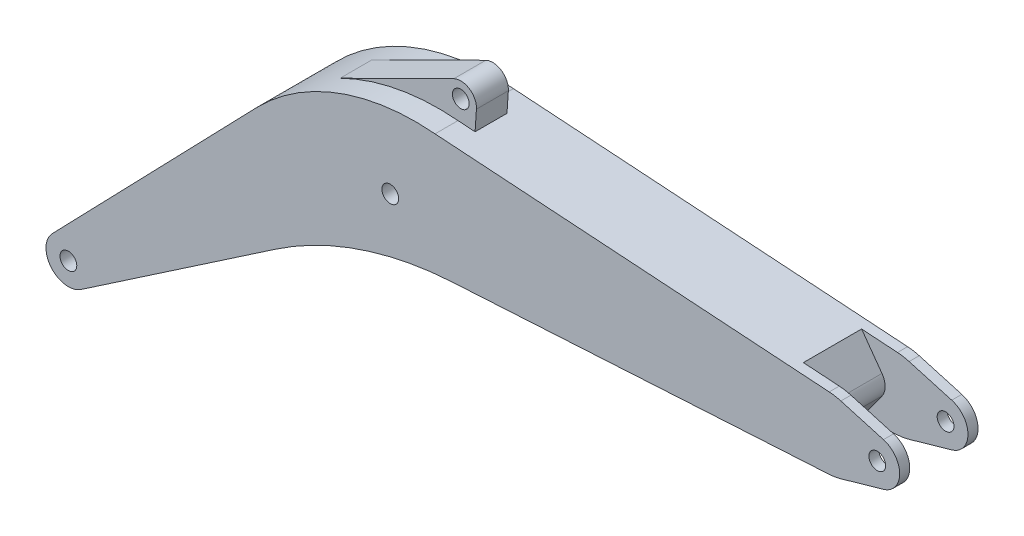
SolidWorks part; units mm, degrees
ref_plane "前视基准面" through (0, 0, 0) normal (0, 0, 1) x (1, 0, 0)
ref_plane "上视基准面" through (0, 0, 0) normal (0, 1, 0) x (1, 0, 0)
ref_plane "右视基准面" through (0, 0, 0) normal (1, 0, 0) x (0, 0, -1)
sketch "草图1" plane through (0, 0, 0) normal (0, 0, 1) x (1, 0, 0)
  line L0 (84.9387, 100.9448) -> (169.1185, 46.9656) construction
  line L1 (163.6, 91.5) -> (232.0719, 95.4882)
  line L2 (232.0719, 95.4882) -> (240.6992, 97.954)
  line L3 (160.6, 112.9) -> (232.0719, 108.1118)
  line L4 (232.0719, 108.1118) -> (240.6992, 105.646)
  line L5 (128.7, 101) -> (92.2246, 63.2806)
  line L6 (97.3478, 57.1913) -> (132.1, 80.8)
  line L7 (95.1, 60.5) -> (239.6, 60.5) construction
  line L8 (239.6, 60.5) -> (239.6, 101.8) construction
  line L9 (239.6, 101.8) -> (95.1, 101.8) construction
  line L10 (95.1, 101.8) -> (95.1, 60.5) construction
  line L11 (152.6, 99.6031) -> (152.6, 60.5) construction
  line L12 (132.1, 80.8) -> (132.1, 60.5) construction
  line L13 (128.7, 101) -> (128.7, 60.5) construction
  line L14 (160.6, 112.9) -> (160.6, 60.5) construction
  line L16 (163.6, 91.5) -> (163.6, 60.5)
  arc A0 (128.7, 101) -> (160.6, 112.9) centre (157.1228, 73.5146) cw
  arc A1 (92.2246, 63.2806) -> (97.3478, 57.1913) centre (95.1, 60.5) ccw
  arc A2 (132.1, 80.8) -> (163.6, 91.5) centre (167.2357, 29.0799) cw
  arc A3 (240.6992, 105.646) -> (240.6992, 97.954) centre (239.6, 101.8) cw
  circle A4 centre (239.6, 101.8) radius 1.5
  circle A5 centre (152.6, 99.6031) radius 1.5
  circle A6 centre (95.1, 60.5) radius 1.5
  dimension "D2" = 4
  dimension "D3" = 3
  dimension "D4" = 4
  dimension "D1" = 100
  dimension "D6" = 33.6
  dimension "D7" = 31
  dimension "D8" = 40.5
  dimension "D10" = 95.1
  dimension "D11" = 60.5
  dimension "D12" = 144.5
  dimension "D13" = 41.3
  dimension "D14" = 3.4
  dimension "D15" = 20.3
  dimension "D16" = 20.5
  dimension "D17" = 8
  dimension "D18" = 3
  dimension "D19" = 52.4
extrude "凸台-拉伸1" add sketch "草图1" along normal blind 7 and the other way blind 7 contours A3 L4 L3 A0 L5 A1 L6 A2 L1 L2 A6 A5 A4 region at (163.6972, 95.3089, 0)
fillet "圆角1" radius 10 2 edges at (232.0719, 95.4882, 0) (232.0719, 108.1118, 0)
sketch "草图3" plane through (0, 0, 0) normal (0, 0, 1) x (1, 0, 0)
  line L0 (160.6, 112.9) -> (231.0129, 108.1827) construction
  line L1 (163.6514, 112.6956) -> (163.8937, 116.3128)
  line L3 (160.6, 112.9) -> (232.0719, 108.1118) construction
  line L4 (159.8555, 119.0082) -> (139.5495, 108.9333)
  line L10 (163.6, 91.5) -> (230.9683, 95.4239)
  line L11 (233.1349, 95.792) -> (240.6992, 97.954)
  line L12 (240.6992, 105.646) -> (233.0925, 107.8201)
  line L13 (231.0129, 108.1827) -> (160.6, 112.9)
  line L14 (128.7, 101) -> (92.2246, 63.2806)
  line L15 (97.3478, 57.1913) -> (132.1, 80.8)
  line L16 (163.6, 91.5) -> (230.9683, 95.4239)
  line L17 (233.1349, 95.792) -> (240.6992, 97.954)
  line L18 (240.6992, 105.646) -> (233.0925, 107.8201)
  line L19 (231.0129, 108.1827) -> (160.6, 112.9)
  line L20 (128.7, 101) -> (92.2246, 63.2806)
  line L21 (97.3478, 57.1913) -> (132.1, 80.8)
  arc A0 (160.6, 112.9) -> (128.7, 101) centre (157.1228, 73.5146) ccw construction
  arc A1 (159.8555, 119.0082) -> (163.8937, 116.3128) centre (161.1, 116.5) cw
  circle A2 centre (161.1, 116.5) radius 1.5
  arc A9 (230.9683, 95.4239) -> (233.1349, 95.792) centre (230.3868, 105.407) ccw
  arc A10 (240.6992, 97.954) -> (240.6992, 105.646) centre (239.6, 101.8) ccw
  arc A11 (233.0925, 107.8201) -> (231.0129, 108.1827) centre (230.3444, 98.2051) ccw
  arc A12 (160.6, 112.9) -> (128.7, 101) centre (157.1228, 73.5146) ccw
  arc A13 (92.2246, 63.2806) -> (97.3478, 57.1913) centre (95.1, 60.5) ccw
  arc A14 (163.6, 91.5) -> (132.1, 80.8) centre (167.2357, 29.0799) ccw
  arc A15 (230.9683, 95.4239) -> (233.1349, 95.792) centre (230.3868, 105.407) ccw
  arc A16 (240.6992, 97.954) -> (240.6992, 105.646) centre (239.6, 101.8) ccw
  arc A17 (233.0925, 107.8201) -> (231.0129, 108.1827) centre (230.3444, 98.2051) ccw
  arc A18 (160.6, 112.9) -> (128.7, 101) centre (157.1228, 73.5146) ccw
  arc A19 (92.2246, 63.2806) -> (97.3478, 57.1913) centre (95.1, 60.5) ccw
  arc A20 (163.6, 91.5) -> (132.1, 80.8) centre (167.2357, 29.0799) ccw
  dimension "D1" = 3
  dimension "D5" = 2.8
  dimension "D3" = 56
  dimension "D4" = 66
  dimension "D2" = 0
extrude "凸台-拉伸2" add sketch "草图3" along normal blind 2.9 and the other way blind 2.8 contours L1 A1 L4 A2 region at (156.7685, 114.8999, 0)
sketch "草图4" plane through (0, 0, 0) normal (0, 0, 1) x (1, 0, 0)
  line L0 (224.6, 108.6124) -> (228.2365, 103.5503)
  line L1 (160.6, 112.9) -> (232.0719, 108.1118) construction
  line L2 (228.2256, 100.0347) -> (224.6, 95.053)
  line L3 (163.6, 91.5) -> (232.0719, 95.4882) construction
  line L4 (239.6, 101.8) -> (224.6, 101.8) construction
  line L5 (224.6, 101.8) -> (224.6, 108.6124) construction
  line L6 (224.6, 101.8) -> (224.6, 95.053) construction
  line L10 (163.6, 91.5) -> (230.9683, 95.4239)
  line L11 (233.1349, 95.792) -> (240.6992, 97.954)
  line L12 (240.6992, 105.646) -> (233.0925, 107.8201)
  line L13 (231.0129, 108.1827) -> (160.6, 112.9)
  line L14 (128.7, 101) -> (92.2246, 63.2806)
  line L15 (97.3478, 57.1913) -> (132.1, 80.8)
  line L16 (163.6, 91.5) -> (230.9683, 95.4239)
  line L17 (233.1349, 95.792) -> (240.6992, 97.954)
  line L18 (240.6992, 105.646) -> (233.0925, 107.8201)
  line L19 (231.0129, 108.1827) -> (160.6, 112.9)
  line L20 (128.7, 101) -> (92.2246, 63.2806)
  line L21 (97.3478, 57.1913) -> (132.1, 80.8)
  arc A0 (228.2365, 103.5503) -> (228.2256, 100.0347) centre (225.8, 101.8) cw
  arc A7 (230.9683, 95.4239) -> (233.1349, 95.792) centre (230.3868, 105.407) ccw
  arc A8 (240.6992, 97.954) -> (240.6992, 105.646) centre (239.6, 101.8) ccw
  arc A9 (233.0925, 107.8201) -> (231.0129, 108.1827) centre (230.3444, 98.2051) ccw
  arc A10 (160.6, 112.9) -> (128.7, 101) centre (157.1228, 73.5146) ccw
  arc A11 (92.2246, 63.2806) -> (97.3478, 57.1913) centre (95.1, 60.5) ccw
  arc A12 (163.6, 91.5) -> (132.1, 80.8) centre (167.2357, 29.0799) ccw
  arc A13 (230.9683, 95.4239) -> (233.1349, 95.792) centre (230.3868, 105.407) ccw
  arc A14 (240.6992, 97.954) -> (240.6992, 105.646) centre (239.6, 101.8) ccw
  arc A15 (233.0925, 107.8201) -> (231.0129, 108.1827) centre (230.3444, 98.2051) ccw
  arc A16 (160.6, 112.9) -> (128.7, 101) centre (157.1228, 73.5146) ccw
  arc A17 (92.2246, 63.2806) -> (97.3478, 57.1913) centre (95.1, 60.5) ccw
  arc A18 (163.6, 91.5) -> (132.1, 80.8) centre (167.2357, 29.0799) ccw
  dimension "D2" = 3
  dimension "D3" = 15
  dimension "D4" = 1.2
  dimension "D1" = 0
extrude "切除-拉伸1" cut sketch "草图4" against normal blind 5.2 and the other way blind 5.2 contours L0 A0 L2 region at (234.0235, 101.8062, 0)
